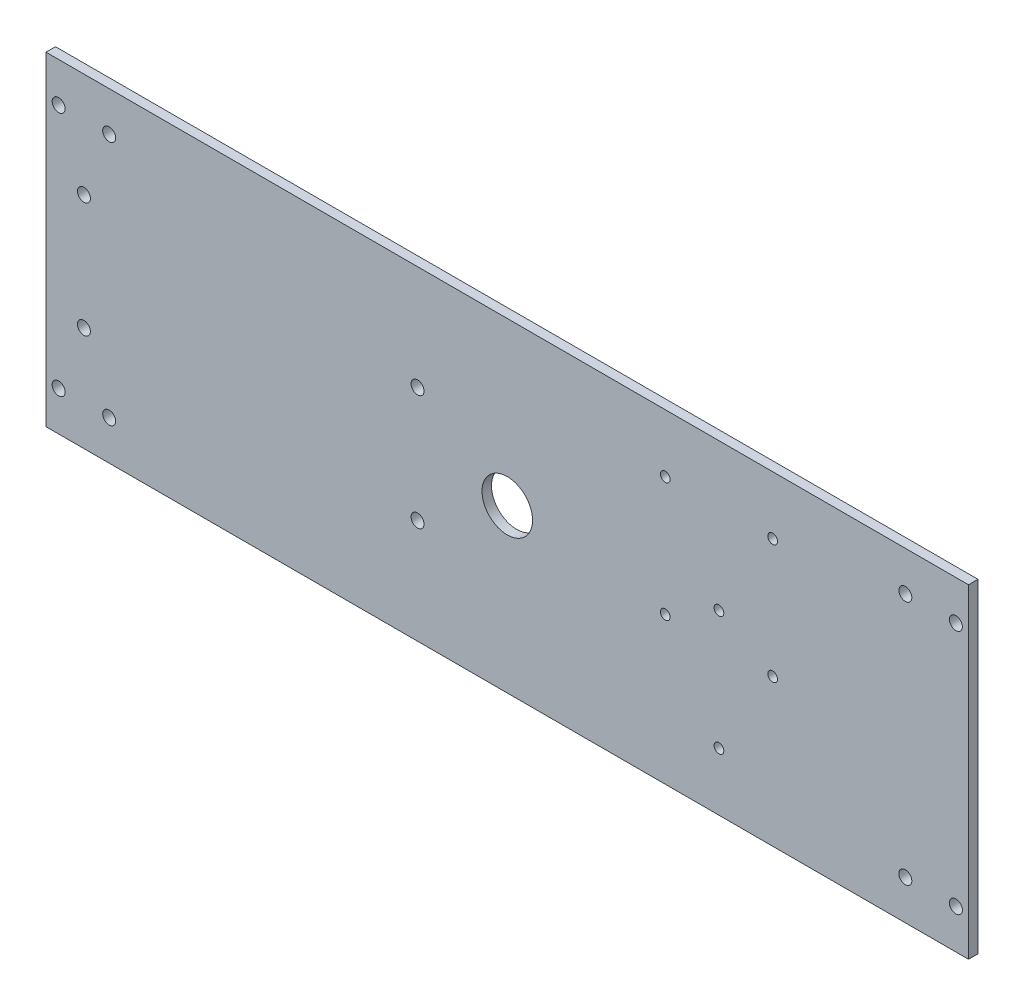
SolidWorks part; units mm, degrees
material "E-Glass Fiber"
ref_plane "Front Plane" through (0, 0, 0) normal (0, 0, 1) x (1, 0, 0)
ref_plane "Top Plane" through (0, 0, 0) normal (0, 1, 0) x (1, 0, 0)
ref_plane "Right Plane" through (0, 0, 0) normal (1, 0, 0) x (0, 0, -1)
sketch "Sketch1" plane through (0, 0, 0) normal (0, 0, 1) x (1, 0, 0)
  line L1 (-115.8875, -40.748) -> (115.8875, -40.748)
  line L2 (-115.8875, -40.748) -> (-115.8875, 40.7479)
  line L3 (-115.8875, 40.7479) -> (115.8875, 40.7479)
  line L4 (115.8875, -40.748) -> (115.8875, 40.7479)
  line L5 (-115.8875, -40.748) -> (115.8875, 40.7479) construction
  line L6 (-115.8875, 40.7479) -> (115.8875, -40.748) construction
  point P0 (0, 0)
  dimension "D1" = 231.775
  dimension "D2" = 81.4959
extrude "Boss-Extrude1" add sketch "Sketch1" along normal blind 2.3813
sketch "Sketch2" plane through (0, 0, 2.3813) normal (0, 0, 1) x (1, 0, 0)
  line L0 (-8.9154, 28.575) -> (29.1846, 28.575) construction
  line L1 (115.8875, 0) -> (111.125, 0) construction
  line L2 (115.8875, -40.748) -> (115.8875, 40.7479) construction
  line L3 (111.125, 0) -> (111.125, 9.525) construction
  line L4 (111.125, 9.525) -> (111.125, 25.4) construction
  line L5 (-115.8875, 0) -> (-111.125, 0) construction
  line L6 (-115.8875, 40.7479) -> (-115.8875, -40.748) construction
  line L7 (-111.125, 0) -> (-111.125, 9.525) construction
  line L8 (-111.125, 9.525) -> (-111.125, 25.4) construction
  line L9 (-115.8875, 30.8204) -> (-112.7125, 30.8204) construction
  line L10 (-112.7125, 30.8204) -> (-100.0125, 30.8204) construction
  dimension "D1" = 38.1
  dimension "D2" = 28.575
  dimension "D3" = 8.9154
  dimension "D4" = 4.7625
  dimension "D5" = 9.525
  dimension "D6" = 25.4
  dimension "D7" = 30.8204
  dimension "D8" = 12.7
  dimension "D9" = 3.175
hole_wizard "#4 Clearance Hole2" positions "Sketch6" profile "Sketch7" hole size "#4" standard "ANSI Inch" end condition through all
sketch "Sketch6" plane through (0, 0, 2.3813) normal (0, 0, 1) x (1, 0, 0)
  point P0 (-112.7125, 30.8204)
  point P3 (-100.0125, 30.8204)
sketch "Sketch7" plane through (-112.7125, 30.8204, 2.3813) normal (1, 0, 0) x (0, -1, 0)
  line L0 (0, 0) -> (0, 2.3813)
  line L1 (0, 2.3813) -> (1.6319, 2.3813)
  line L2 (1.6319, 2.3813) -> (1.6319, 0)
  line L5 (1.6319, 0) -> (0, 0)
  line L11 (0, -6.35) -> (0, 107.95) construction
  dimension "Thru Hole Dia." = 3.2639
  dimension "Thru Hole Depth" = 2.3813
mirror "Mirror2" about plane through (0, 0, 0) normal (1, 0, 0) of "#4 Clearance Hole2"
mirror "Mirror3" about plane through (0, 0, 0) normal (0, 1, 0) of "Mirror2"
hole_wizard "1/2 (0.5) Diameter Hole1" positions "Sketch9" profile "Sketch8" hole size "1/2" standard "ANSI Inch" end condition through all
sketch "Sketch9" plane through (0, 0, 2.3813) normal (0, 0, 1) x (1, 0, 0)
  point P0 (0, 0)
sketch "Sketch8" plane through (0, 0, 2.3813) normal (1, 0, 0) x (0, -1, 0)
  line L0 (0, 0) -> (0, 2.3812)
  line L1 (0, 2.3812) -> (6.35, 2.3812)
  line L2 (6.35, 2.3812) -> (6.35, 0)
  line L5 (6.35, 0) -> (0, 0)
  line L11 (0, -6.35) -> (0, 107.95) construction
  dimension "Thru Hole Dia." = 12.7
  dimension "Thru Hole Depth" = 2.3813
sketch "Sketch10" plane through (0, 0, 2.3813) normal (0, 0, 1) x (1, 0, 0)
  line L0 (0, 0) -> (-64.4525, 0) construction
  line L1 (-106.3625, -14.478) -> (-22.5425, -14.478) construction
  line L2 (-106.3625, -14.478) -> (-106.3625, 14.478) construction
  line L3 (-106.3625, 14.478) -> (-22.5425, 14.478) construction
  line L4 (-22.5425, -14.478) -> (-22.5425, 14.478) construction
  line L5 (-106.3625, -14.478) -> (-22.5425, 14.478) construction
  line L6 (-106.3625, 14.478) -> (-22.5425, -14.478) construction
  line L7 (-115.8875, 40.7479) -> (-115.8875, -40.748) construction
  line L8 (39.697, 26.162) -> (66.6718, 26.162) construction
  line L9 (53.1844, 26.162) -> (53.1844, 3.81) construction
  line L10 (0, 0) -> (53.1844, 0) construction
  line L11 (53.1844, 0) -> (53.1844, 3.81) construction
  point P0 (-64.4525, 0)
  dimension "D1" = 83.82
  dimension "D2" = 28.956
  dimension "D3" = 9.525
  dimension "D4" = 13.4874
  dimension "D5" = 22.352
  dimension "D6" = 26.9748
  dimension "D7" = 3.81
hole_wizard "#4 Clearance Hole3" positions "Sketch12" profile "Sketch13" hole size "#4" standard "ANSI Inch" end condition through all
sketch "Sketch12" plane through (0, 0, 2.3813) normal (0, 0, 1) x (1, 0, 0)
  point P0 (-106.3625, 14.478)
  point P3 (-22.5425, 14.478)
  point P6 (-22.5425, -14.478)
  point P9 (-106.3625, -14.478)
sketch "Sketch13" plane through (-106.3625, 14.478, 2.3813) normal (1, 0, 0) x (0, -1, 0)
  line L0 (0, 0) -> (0, 2.3813)
  line L1 (0, 2.3813) -> (1.6319, 2.3813)
  line L2 (1.6319, 2.3813) -> (1.6319, 0)
  line L5 (1.6319, 0) -> (0, 0)
  line L11 (0, -6.35) -> (0, 107.95) construction
  dimension "Thru Hole Dia." = 3.2639
  dimension "Thru Hole Depth" = 2.3813
hole_wizard "#2 Clearance Hole1" positions "Sketch15" profile "Sketch16" hole size "#2" standard "ANSI Inch" end condition through all
sketch "Sketch15" plane through (0, 0, 2.3813) normal (0, 0, 1) x (1, 0, 0)
  point P0 (53.1844, 3.81)
  point P3 (39.697, 26.162)
  point P6 (66.6718, 26.162)
sketch "Sketch16" plane through (53.1844, 3.81, 2.3813) normal (1, 0, 0) x (0, -1, 0)
  line L0 (0, 0) -> (0, 2.3813)
  line L1 (0, 2.3813) -> (1.2192, 2.3813)
  line L2 (1.2192, 2.3813) -> (1.2192, 0)
  line L5 (1.2192, 0) -> (0, 0)
  line L11 (0, -6.35) -> (0, 107.95) construction
  dimension "Thru Hole Dia." = 2.4384
  dimension "Thru Hole Depth" = 2.3813
pattern_linear "LPattern1" count 2 spacing 29.972 along (0, -1, 0) of "#2 Clearance Hole1"
